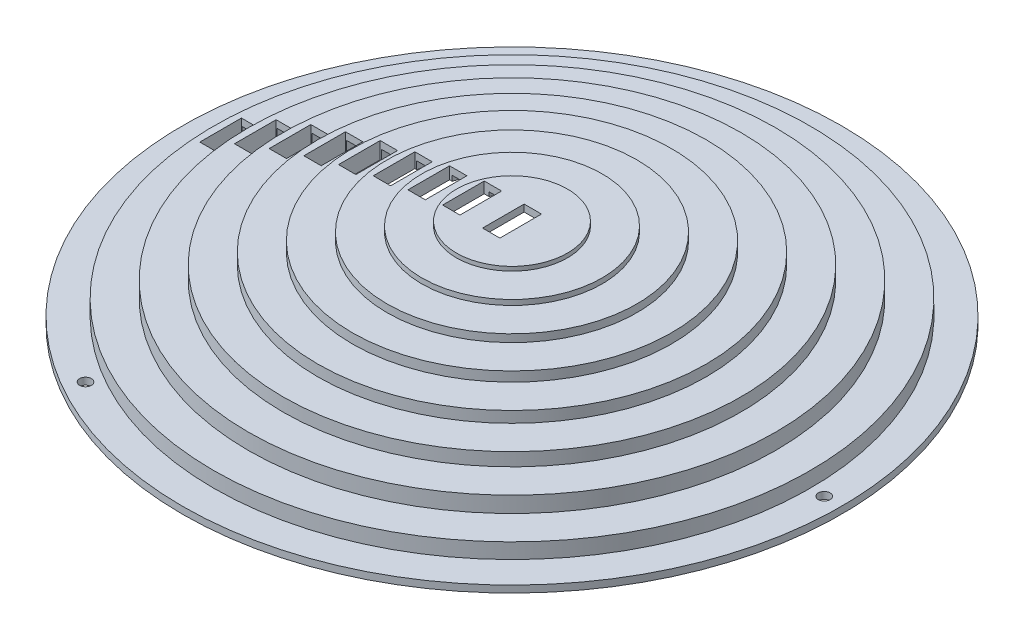
SolidWorks part; units mm, degrees
ref_plane "Plan de face" through (0, 0, 0) normal (0, 0, 1) x (1, 0, 0)
ref_plane "Plan de dessus" through (0, 0, 0) normal (0, 1, 0) x (1, 0, 0)
ref_plane "Plan de droite" through (0, 0, 0) normal (1, 0, 0) x (0, 0, -1)
sketch "Esquisse7" plane through (0, 0, 0) normal (0, 0, 1) x (1, 0, 0)
  line L0 (-86.5, 4.4116) -> (86.5, 4.4116)
  line L1 (-37.2068, 24.4116) -> (31.8591, 24.4116) construction
  line L2 (-95, 0) -> (95, 0)
  arc A1 (-95, 0) -> (95, 0) centre (0, -172.6446) cw
  point P4 (0, 4.4116)
  point P10 (0, 0)
  dimension "D1" = 173
  dimension "D2" = 20
  dimension "D3" = 190
sketch "Esquisse1" plane through (0, 0, 0) normal (0, 1, 0) x (1, 0, 0)
  circle A0 centre (0, 0) radius 86
  circle A1 centre (0, 0) radius 76
  circle A2 centre (0, 0) radius 66
  circle A3 centre (0, 0) radius 56
  circle A4 centre (0, 0) radius 46
  circle A6 centre (0, 0) radius 36
  circle A7 centre (0, 0) radius 26
  circle A8 centre (0, 0) radius 16
  circle A9 centre (0, 0) radius 6
  circle A10 centre (0, 0) radius 95
  dimension "D1" = 172
  dimension "D2" = 152
  dimension "132" = 132
  dimension "D4" = 112
  dimension "D5" = 92
  dimension "D6" = 72
  dimension "D7" = 52
  dimension "D8" = 32
  dimension "D9" = 12
  dimension "D10" = 190
extrude "Boss.-Extru.1" add sketch "Esquisse1" against normal blind 2 contours A10
extrude "Boss.-Extru.11" add sketch "Esquisse1<12>" along normal blind 4.42 contours A0 A1 region at (-83.5676, 0, 0)
sketch "Esquisse1<12>" plane through (0, 0, 0) normal (0, 1, 0) x (1, 0, 0) same geometry as "Esquisse1"
extrude "Boss.-Extru.3" add sketch "Esquisse1<4>" along normal blind 9 contours A1
sketch "Esquisse1<4>" plane through (0, 0, 0) normal (0, 1, 0) x (1, 0, 0) same geometry as "Esquisse1"
extrude "Boss.-Extru.4" add sketch "Esquisse1<5>" along normal blind 12.8 contours A2
sketch "Esquisse1<5>" plane through (0, 0, 0) normal (0, 1, 0) x (1, 0, 0) same geometry as "Esquisse1"
extrude "Boss.-Extru.5" add sketch "Esquisse1<6>" along normal blind 16 contours A3
sketch "Esquisse1<6>" plane through (0, 0, 0) normal (0, 1, 0) x (1, 0, 0) same geometry as "Esquisse1"
extrude "Boss.-Extru.6" add sketch "Esquisse1<7>" along normal blind 18.8 contours A4
sketch "Esquisse1<7>" plane through (0, 0, 0) normal (0, 1, 0) x (1, 0, 0) same geometry as "Esquisse1"
extrude "Boss.-Extru.7" add sketch "Esquisse1<8>" along normal blind 21 contours A6
sketch "Esquisse1<8>" plane through (0, 0, 0) normal (0, 1, 0) x (1, 0, 0) same geometry as "Esquisse1"
extrude "Boss.-Extru.8" add sketch "Esquisse1<9>" along normal blind 22.5 contours A7
sketch "Esquisse1<9>" plane through (0, 0, 0) normal (0, 1, 0) x (1, 0, 0) same geometry as "Esquisse1"
extrude "Boss.-Extru.9" add sketch "Esquisse1<10>" along normal blind 23.7 contours A8
sketch "Esquisse1<10>" plane through (0, 0, 0) normal (0, 1, 0) x (1, 0, 0) same geometry as "Esquisse1"
shell "Coque1" thickness 2 removed face at (0, -2, 95)
sketch "Esquisse4" plane through (0, 23.7, 0) normal (0, 1, 0) x (1, 0, 0)
  line L0 (-24, 6) -> (-19, 6)
  line L1 (-2.5, 6) -> (2.5, 6)
  line L2 (-2.5, 6) -> (-2.5, -6)
  line L3 (-2.5, -6) -> (2.5, -6)
  line L4 (2.5, 6) -> (2.5, -6)
  line L5 (-2.5, 6) -> (2.5, -6) construction
  line L6 (-2.5, -6) -> (2.5, 6) construction
  line L7 (-19, 6) -> (-19, -6)
  line L8 (-14, 6) -> (-9, 6)
  line L9 (-14, 6) -> (-14, -6)
  line L10 (-14, -6) -> (-9, -6)
  line L11 (-9, 6) -> (-9, -6)
  line L12 (-14, 6) -> (-9, -6) construction
  line L13 (-14, -6) -> (-9, 6) construction
  line L14 (-24, -6) -> (-19, -6)
  line L15 (-24, 6) -> (-24, -6)
  line L16 (-34, 6) -> (-29, 6)
  line L17 (-29, 6) -> (-29, -6)
  line L18 (-34, -6) -> (-29, -6)
  line L19 (-34, 6) -> (-34, -6)
  line L20 (-44, 6) -> (-39, 6)
  line L21 (-39, 6) -> (-39, -6)
  line L22 (-44, -6) -> (-39, -6)
  line L23 (-44, 6) -> (-44, -6)
  line L24 (-54, 6) -> (-49, 6)
  line L25 (-49, 6) -> (-49, -6)
  line L26 (-54, -6) -> (-49, -6)
  line L27 (-54, 6) -> (-54, -6)
  line L28 (-64, 6) -> (-59, 6)
  line L29 (-59, 6) -> (-59, -6)
  line L30 (-64, -6) -> (-59, -6)
  line L31 (-64, 6) -> (-64, -6)
  line L32 (-74, 6) -> (-69, 6)
  line L33 (-69, 6) -> (-69, -6)
  line L34 (-74, -6) -> (-69, -6)
  line L35 (-74, 6) -> (-74, -6)
  line L36 (-84, 6) -> (-79, 6)
  line L37 (-79, 6) -> (-79, -6)
  line L38 (-84, -6) -> (-79, -6)
  line L39 (-84, 6) -> (-84, -6)
  circle A0 centre (0, 0) radius 11.5 construction
  point P1 (0, 0)
  point P8 (-12.8768, 0.499)
  point P9 (-11.5, 0)
  point P14 (0, 0)
  dimension "D3" = 23
  dimension "D1" = 5
  dimension "D2" = 12
  dimension "D4" = 8
extrude "Enlèv. mat.-Extru.2" cut sketch "Esquisse4" against normal through all
hole_wizard "Dégagement M31" positions "Esquisse5" profile "Esquisse6" hole size "M3" standard "ISO" end condition through all
sketch "Esquisse5" plane through (0, 0, 0) normal (0, 1, 0) x (1, 0, 0)
  line L1 (-45, 77.9423) -> (-45, -77.9423) construction
  line L2 (-45, -77.9423) -> (90, 0) construction
  line L3 (90, 0) -> (-45, 77.9423) construction
  circle A0 centre (0, 0) radius 45 construction
  point P3 (-45, 77.9423)
  point P4 (-45, -77.9423)
  point P5 (90, 0)
  dimension "D1" = 90
sketch "Esquisse6" plane through (90, 0, 0) normal (1, 0, 0) x (0, 0, 1)
  line L0 (0, 0) -> (0, 2)
  line L1 (0, 2) -> (1.7, 2)
  line L2 (1.7, 2) -> (1.7, 0)
  line L5 (1.7, 0) -> (0, 0)
  line L11 (0, -6.35) -> (0, 107.95) construction
  dimension "Diamètre du perçage jusqu'au prochain" = 3.4
  dimension "Profondeur du perçage jusqu'au prochain" = 2
